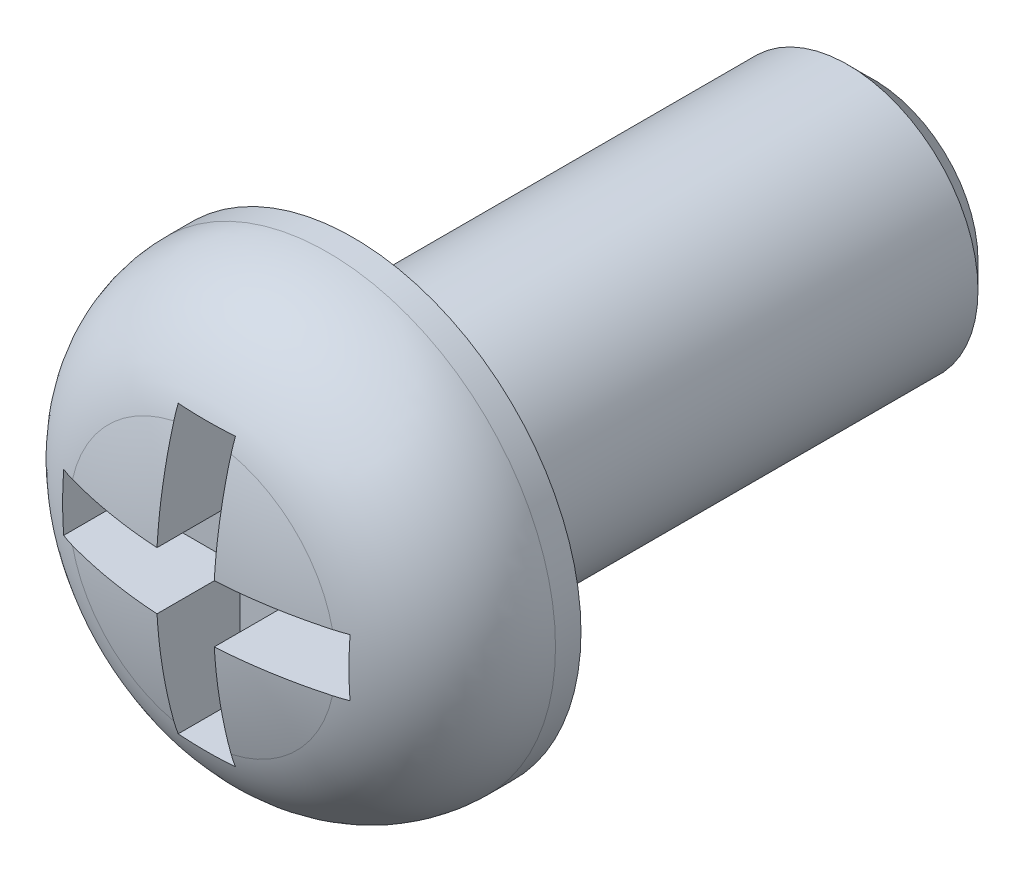
SolidWorks part; units mm, degrees
ref_plane "Front" through (0, 0, 0) normal (0, 0, 1) x (1, 0, 0)
ref_plane "Top" through (0, 0, 0) normal (0, 1, 0) x (1, 0, 0)
ref_plane "Right" through (0, 0, 0) normal (1, 0, 0) x (0, 0, -1)
sketch "Sketch1" plane through (0, 0, 0) normal (1, 0, 0) x (0, 0, -1)
  line L0 (-33.736, 0) -> (50.0028, 0) construction
  line L1 (-0.8667, 1.75) -> (0, 1.75)
  line L2 (0, 1.75) -> (0, 1)
  line L3 (0, 1) -> (4, 1)
  line L6 (4, 0) -> (-1.3, 0)
  line L8 (4, 1) -> (4, 0)
  arc A0 (-1.3, 0) -> (-0.8667, 1.75) centre (2.4503, 0) cw
  dimension "D1" = 2
  dimension "D2" = 0.8667
  dimension "l" = 4
  dimension "k+f" = 1.3
  dimension "dk" = 3.5
revolve "Revolve1" add sketch "Sketch1" angle 360 about L0
ref_plane "Plane1" through (0, 0, 1.3) normal (0, 0, -1) x (-1, 0, 0)
sketch "Sketch2" plane through (0, 0, 1.3) normal (0, 0, -1) x (-1, 0, 0)
  line L0 (0, 2.0016) -> (0, -1.8677) construction
  line L1 (2.0756, 0) -> (-1.9911, 0) construction
  line L2 (0, 1.1) -> (0.22, 1.1)
  line L3 (0.22, 1.1) -> (0.22, 0.22)
  line L4 (0.22, 0.22) -> (1.1, 0.22)
  line L5 (1.1, 0.22) -> (1.1, 0)
  line L6 (0.22, -1.1) -> (0, -1.1)
  line L7 (0.22, -0.22) -> (0.22, -1.1)
  line L8 (1.1, -0.22) -> (0.22, -0.22)
  line L9 (1.1, 0) -> (1.1, -0.22)
  line L10 (-1.1, -0.22) -> (-1.1, 0)
  line L11 (-0.22, -0.22) -> (-1.1, -0.22)
  line L12 (-0.22, -1.1) -> (-0.22, -0.22)
  line L13 (0, -1.1) -> (-0.22, -1.1)
  line L14 (-0.22, 1.1) -> (0, 1.1)
  line L15 (-0.22, 0.22) -> (-0.22, 1.1)
  line L16 (-1.1, 0.22) -> (-0.22, 0.22)
  line L17 (-1.1, 0) -> (-1.1, 0.22)
  dimension "D1" = 0.22
  dimension "m1/2" = 1.1
  dimension "D3" = 0.22
  dimension "m2/2" = 1.1
extrude "Cut-Extrude2" cut sketch "Sketch2" along normal blind 0.65
fillet "Fillet1" radius 1 1 edges at (1.75, 0, 0.8667)
chamfer "Chamfer1" distance 0.2 1 edges at (1, 0, -4)
equation "\"D1@Sketch2\" = \"m1/2@Sketch2\"/5"
equation "\"D3@Sketch2\" = \"m2/2@Sketch2\"/5"
equation "\"D1@Plane1\" = \"k+f@Sketch1\""
equation "\"D1@Cut-Extrude2\" = \"k+f@Sketch1\"/2"
equation "\"D2@Sketch1\" = \"k+f@Sketch1\"*2/3"
